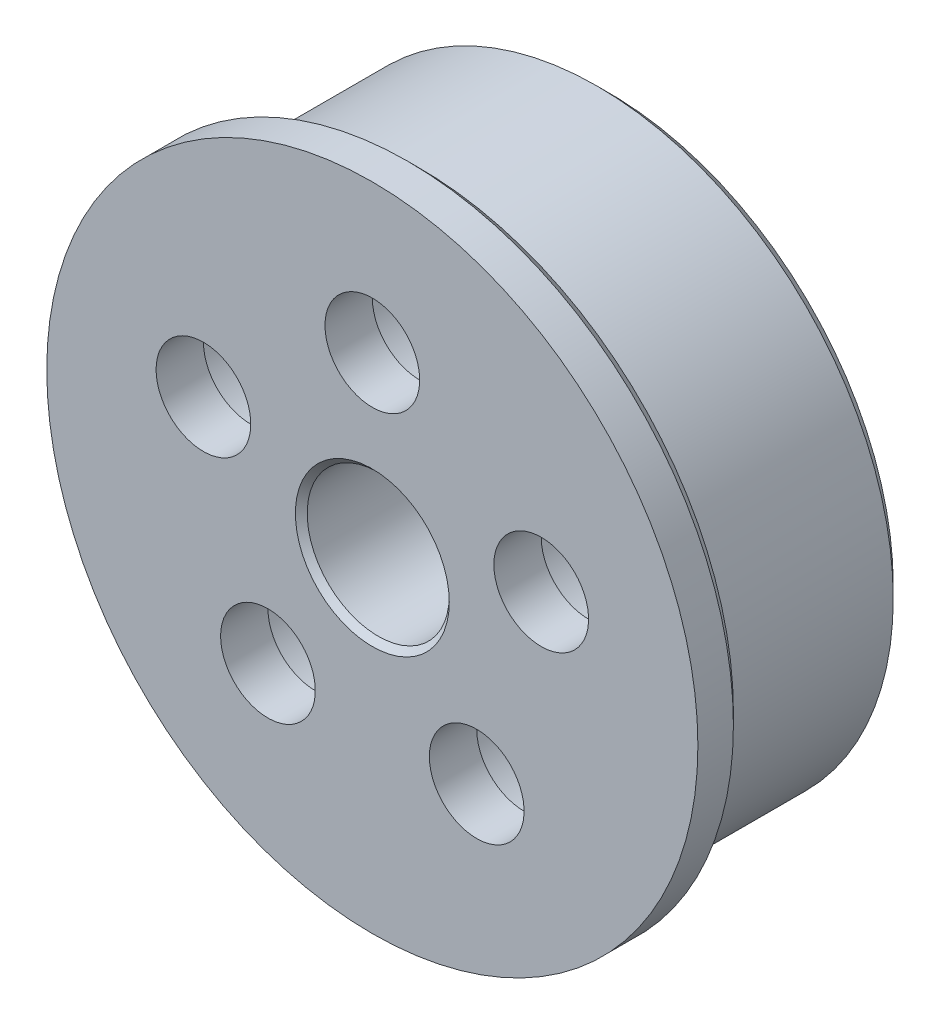
SolidWorks part; units mm, degrees
material "A2017"
ref_plane "正面" through (0, 0, 0) normal (0, 0, 1) x (1, 0, 0)
ref_plane "平面" through (0, 0, 0) normal (0, 1, 0) x (1, 0, 0)
ref_plane "右側面" through (0, 0, 0) normal (1, 0, 0) x (0, 0, -1)
sketch "ｽｹｯﾁ1" plane through (0, 0, 0) normal (0, 0, 1) x (1, 0, 0)
  circle A0 centre (0, 0) radius 12.5
  circle A1 centre (0, 7.5) radius 1.5
  circle A2 centre (0, 0) radius 7.5 construction
  circle A3 centre (7.1329, 2.3176) radius 1.5
  circle A4 centre (4.4084, -6.0676) radius 1.5
  circle A5 centre (-4.4084, -6.0676) radius 1.5
  circle A6 centre (-7.1329, 2.3176) radius 1.5
  point P16 (0, 0)
  dimension "D1" = 25
  dimension "D2" = 15
  dimension "D3" = 3
  dimension "D4" = 5
extrude "ﾎﾞｽ - 押し出し1" add sketch "ｽｹｯﾁ1" along normal blind 10
sketch "ｽｹｯﾁ3" plane through (0, 0, 10) normal (0, 0, 1) x (1, 0, 0)
  circle A0 centre (0, 0) radius 13.75
  circle A2 centre (0, 0) radius 12.5
  circle A3 centre (0, 0) radius 12.5
  dimension "D1" = 0
  dimension "D2" = 27.5
extrude "ﾎﾞｽ - 押し出し3" add sketch "ｽｹｯﾁ3" against normal blind 2
sketch "ｽｹｯﾁ4" plane through (0, 0, 0) normal (0, 0, -1) x (-1, 0, 0)
  circle A0 centre (0, 0) radius 3
  dimension "D1" = 6
extrude "ｶｯﾄ - 押し出し1" cut sketch "ｽｹｯﾁ4" against normal through all
hole_wizard "M3 穴付きねじ用座ぐり穴1" positions "ｽｹｯﾁ5" profile "ｽｹｯﾁ6" counterbore size "M3" standard "JIS" end condition through all
sketch "ｽｹｯﾁ5" plane through (0, 0, 0) normal (0, 0, -1) x (-1, 0, 0)
  point P0 (0, 7.5)
  point P3 (7.1329, 2.3176)
  point P6 (4.4084, -6.0676)
  point P9 (-4.4084, -6.0676)
  point P12 (-7.1329, 2.3176)
sketch "ｽｹｯﾁ6" plane through (0, 7.5, 0) normal (1, 0, 0) x (0, 1, 0)
  line L0 (0, 0) -> (0, 10)
  line L1 (0, 10) -> (2, 10)
  line L3 (2, 10) -> (2, 8)
  line L4 (2, 8) -> (3.5, 8)
  line L5 (3.5, 8) -> (3.5, 0)
  line L7 (3.5, 0) -> (0, 0)
  line L11 (0, -6.35) -> (0, 107.95) construction
  dimension "通し穴の直径" = 4
  dimension "通し穴の深さ" = 10
  dimension "座ぐり穴の直径" = 7
  dimension "座ぐり穴の深さ" = 8
chamfer "面取り1" distance 0.5 angle 45 2 edges at (12.5, 0, 0) (13.75, 0, 8)
chamfer "面取り2" distance 0.25 angle 45 7 edges at (-3, 0, 0) (-3, 0, 10) (0.9084, -6.0676, 0) (-7.9084, -6.0676, 0) (-10.6329, 2.3176, 0) (-3.5, 7.5, 0) (3.6329, 2.3176, 0)
